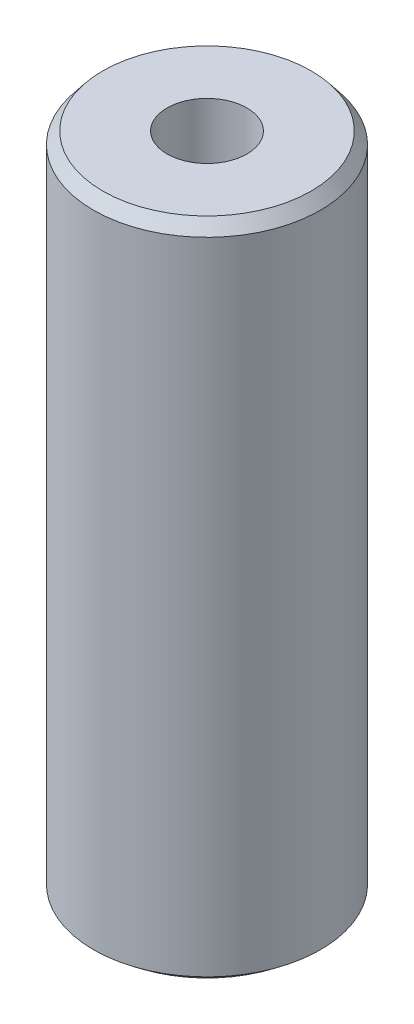
SolidWorks part; units mm, degrees
ref_plane "Front Plane" through (0, 0, 0) normal (0, 0, 1) x (1, 0, 0)
ref_plane "Top Plane" through (0, 0, 0) normal (0, 1, 0) x (1, 0, 0)
ref_plane "Right Plane" through (0, 0, 0) normal (1, 0, 0) x (0, 0, -1)
sketch "Sketch1" plane through (0, 0, 0) normal (0, 1, 0) x (1, 0, 0)
  circle A0 centre (0, 0) radius 45
  dimension "SHAFT_OD" = 90
extrude "Boss-Extrude1" add sketch "Sketch1" along normal blind 262.2288
sketch "Sketch2" plane through (0, 0, 0) normal (0, 1, 0) x (1, 0, 0)
  circle A0 centre (0, 0) radius 15.8208
  dimension "BORE_D" = 31.6417
extrude "Cut-Extrude1" cut sketch "Sketch2" along normal through all
chamfer "Chamfer1" distance 4.6957 angle 38.343 2 edges at (0, 262.2288, 45) (0, 0, 45) first distance on face at (0, 262.2288, 45) first distance on face at (0, 0, 15.8208)
